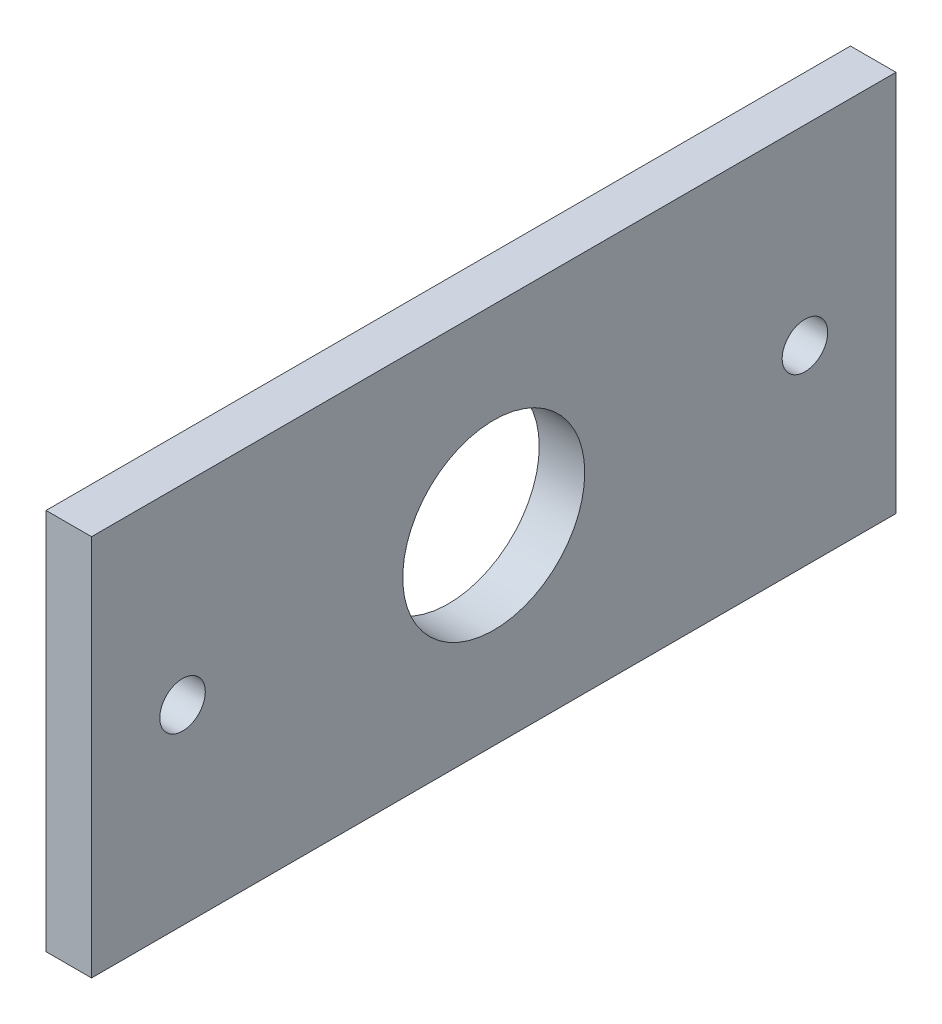
SolidWorks part; units mm, degrees
ref_plane "Front Plane" through (0, 0, 0) normal (0, 0, 1) x (1, 0, 0)
ref_plane "Top Plane" through (0, 0, 0) normal (0, 1, 0) x (1, 0, 0)
ref_plane "Right Plane" through (0, 0, 0) normal (1, 0, 0) x (0, 0, -1)
sketch "Sketch1" plane through (0, 0, 0) normal (1, 0, 0) x (0, 0, -1)
  line L1 (-56.134, -26.67) -> (56.134, -26.67)
  line L2 (-56.134, -26.67) -> (-56.134, 26.67)
  line L3 (-56.134, 26.67) -> (56.134, 26.67)
  line L4 (56.134, -26.67) -> (56.134, 26.67)
  line L5 (-56.134, -26.67) -> (56.134, 26.67) construction
  line L6 (-56.134, 26.67) -> (56.134, -26.67) construction
  circle A0 centre (0, 0) radius 12.7
  circle A1 centre (-43.434, 0) radius 3.175
  circle A2 centre (43.434, 0) radius 3.175
  point P0 (0, 0)
  dimension "D3" = 25.4
  dimension "D4" = 6.35
  dimension "D5" = 6.35
  dimension "D6" = 12.7
  dimension "D7" = 12.7
  dimension "D1" = 112.268
  dimension "D2" = 53.34
extrude "Boss-Extrude1" add sketch "Sketch1" along normal blind 6.35
